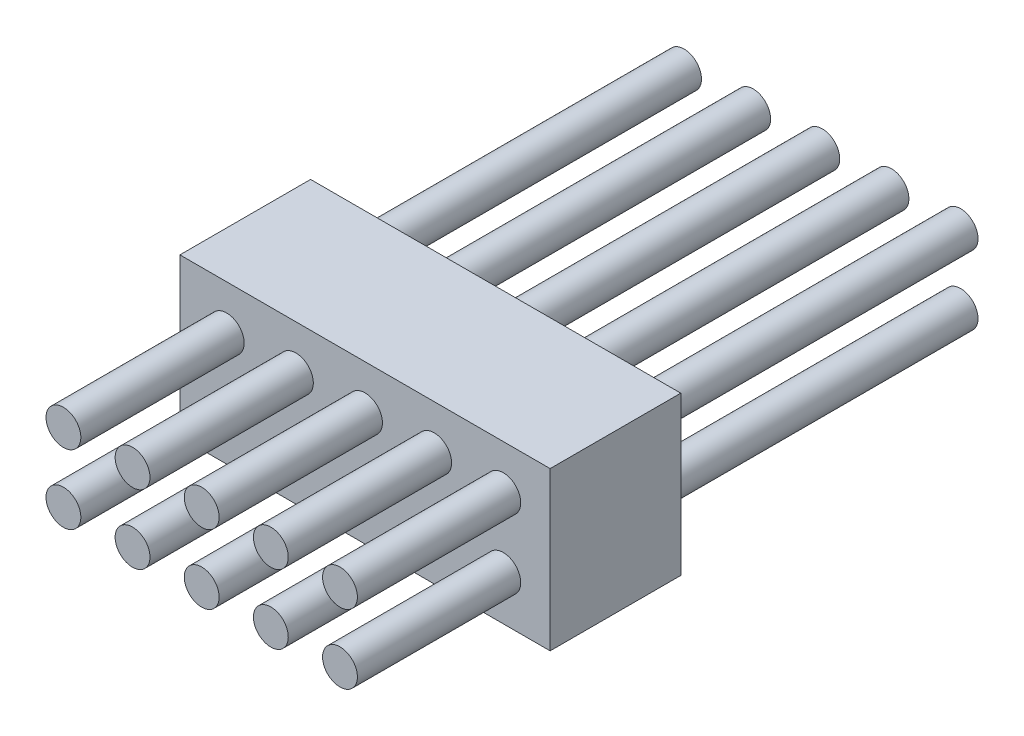
SolidWorks part; units mm, degrees
ref_plane "前视基准面" through (0, 0, 0) normal (0, 0, 1) x (1, 0, 0)
ref_plane "上视基准面" through (0, 0, 0) normal (0, 1, 0) x (1, 0, 0)
ref_plane "右视基准面" through (0, 0, 0) normal (1, 0, 0) x (0, 0, -1)
sketch "Sketch1" plane through (0, 0, 0) normal (0, 0, 1) x (1, 0, 0)
  line L1 (0, 0) -> (6.8, 0)
  line L2 (0, 0) -> (0, 2.9)
  line L3 (0, 2.9) -> (6.8, 2.9)
  line L4 (6.8, 0) -> (6.8, 2.9)
extrude "Boss-Extrude1" add sketch "Sketch1" along normal blind 2.4
sketch "Sketch2" plane through (0, 0, 2.4) normal (0, 0, 1) x (1, 0, 0)
  line L0 (3.4, 2.9) -> (3.4, -1.1111) construction
  line L1 (6.8, 2.9) -> (0, 2.9) construction
  line L2 (0, 1.45) -> (8.011, 1.45) construction
  line L3 (0, 2.9) -> (0, 0) construction
  circle A0 centre (0.86, 0.815) radius 0.32
  circle A1 centre (0.86, 2.085) radius 0.32
  circle A2 centre (2.13, 2.085) radius 0.32
  circle A3 centre (2.13, 0.815) radius 0.32
  circle A4 centre (3.4, 2.085) radius 0.32
  circle A5 centre (3.4, 0.815) radius 0.32
  circle A6 centre (4.67, 2.085) radius 0.32
  circle A7 centre (4.67, 0.815) radius 0.32
  circle A8 centre (5.94, 2.085) radius 0.32
  circle A9 centre (5.94, 0.815) radius 0.32
  dimension "D1" = 0.64
  dimension "D2" = 0.635
  dimension "D3" = 2.54
  dimension "D4" = 5
extrude "Boss-Extrude2" add sketch "Sketch2" along normal blind 3
extrude "Boss-Extrude3" add sketch "Sketch2<2>" against normal blind 6 from surface starting at face at (3.4, 1.45, 0)
sketch "Sketch2<2>" plane through (0, 0, 2.4) normal (0, 0, 1) x (1, 0, 0) same geometry as "Sketch2"
